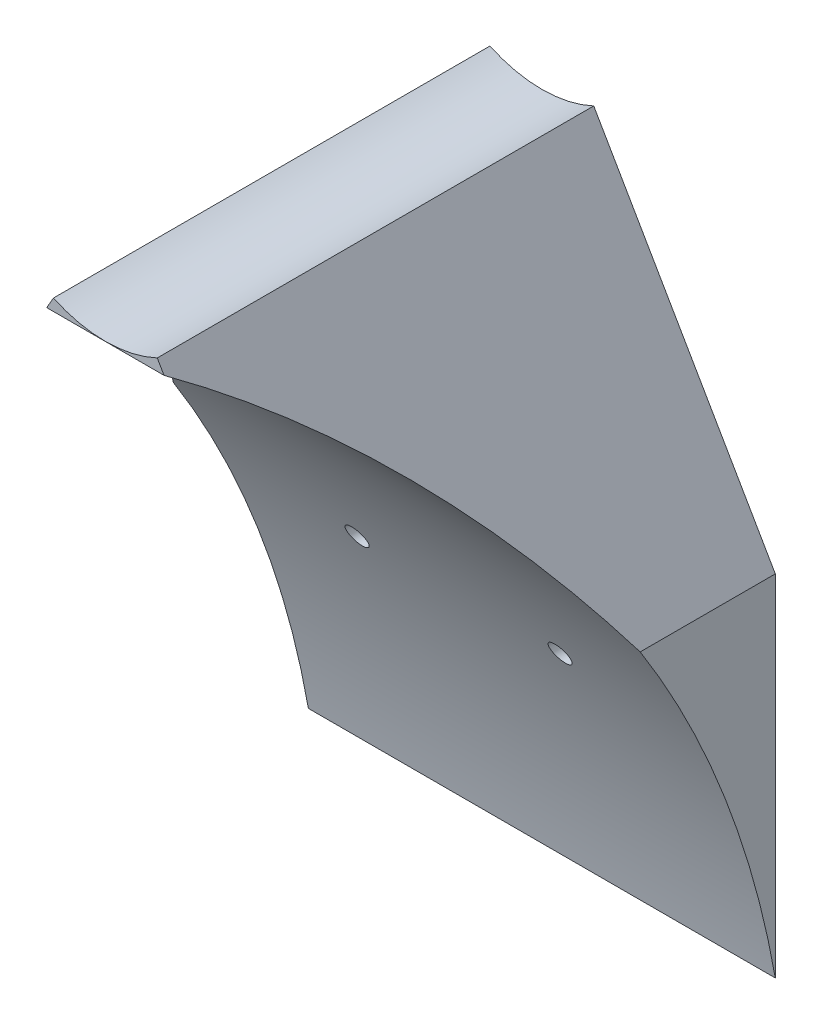
SolidWorks part; units mm, degrees
ref_plane "Front Plane" through (0, 0, 0) normal (0, 0, 1) x (1, 0, 0)
ref_plane "Top Plane" through (0, 0, 0) normal (0, 1, 0) x (1, 0, 0)
ref_plane "Right Plane" through (0, 0, 0) normal (1, 0, 0) x (0, 0, -1)
sketch "Sketch1" plane through (0, 0, 0) normal (0, 0, 1) x (1, 0, 0)
  line L0 (0, 0) -> (0, -127) construction
  line L1 (0, 0) -> (38.1, -65.9911) construction
  line L2 (0, 0) -> (-38.1, -65.9911) construction
  line L3 (-38.1, -65.9911) -> (-38.1, -121.1503) construction
  line L5 (0, 0) -> (0, -127) construction
  line L6 (38.1, -121.1503) -> (38.1, -65.9911) construction
  line L7 (38.1, -121.1503) -> (38.1, -159.2503) construction
  line L8 (-50.8, -197.3503) -> (0, -197.3503) construction
  line L9 (-50.8, -195.7628) -> (0, -195.7628) construction
  line L10 (36.5125, -121.1503) -> (36.5125, -159.2503) construction
  line L11 (36.5125, -121.1503) -> (36.5125, -66.4165)
  line L12 (0, -3.175) -> (36.5125, -66.4165)
  line L13 (0, -3.175) -> (-36.5125, -66.4165)
  line L14 (-36.5125, -66.4165) -> (-36.5125, -121.1503)
  line L15 (-36.5125, -121.1503) -> (-38.1, -121.1503) construction
  line L16 (-50.8, -195.7628) -> (-50.8, -197.3503) construction
  line L17 (36.5125, -121.1503) -> (-36.5125, -121.1503)
  circle A0 centre (0, 0) radius 127 construction
  circle A1 centre (0, 0) radius 76.2 construction
  arc A2 (38.1, -159.2503) -> (0, -197.3503) centre (0, -159.2503) cw construction
  arc A3 (36.5125, -159.2503) -> (0, -195.7628) centre (0, -159.2503) cw construction
  point P2 (-15.875, -74.528)
  point P12 (0, 0)
  point P14 (15.875, -74.528)
  point P25 (0, -38.1)
  dimension "D2" = 152.4
  dimension "D6" = 1.5875
  dimension "D1" = 127
  dimension "D3" = 38.1
  dimension "D4" = 50.8
  dimension "D5" = 60
  dimension "D7" = 38.1
  dimension "D8" = 31.75
extrude "Boss-Extrude1" add sketch "Sketch1" along normal blind 76.2
sketch "Sketch2" plane through (0, 0, 0) normal (1, 0, 0) x (0, 0, -1)
  line L3 (-76.2, -121.1503) -> (0, -121.1503) construction
  line L4 (-76.2, -121.1503) -> (-76.2, -66.4165) construction
  line L6 (-76.2, -121.1503) -> (0, -121.1503)
  line L7 (-76.2, -121.1503) -> (-76.2, -66.4165)
  line L10 (-76.2, -66.4165) -> (-76.2, -3.175) construction
  line L11 (-76.2, -22.225) -> (-76.2, -66.4165)
  line L12 (0, -66.4165) -> (0, -3.175) construction
  line L13 (-76.2, -3.175) -> (0, -3.175) construction
  line L14 (-68.2625, -19.0675) -> (-68.2625, -3.175)
  line L15 (-68.2625, -3.175) -> (-76.2, -3.175)
  line L16 (-76.2, -3.175) -> (-76.2, -22.225)
  arc A0 (-68.2625, -19.0675) -> (0, -121.1503) centre (-150.0796, -147.6432) cw
  dimension "D1" = 68.2625
  dimension "D2" = 152.4
extrude "Cut-Extrude1" cut sketch "Sketch2" along normal up to surface (36.5125 mm away) from surface up to face at (36.5125, -93.7834, 38.1) starting at face at (-36.5125, -93.7834, 38.1)
sketch "Sketch5" plane through (0, 0, 0) normal (0, 0, 1) x (1, 0, 0)
  line L0 (0, -82.55) -> (0, 0) construction
  circle A0 centre (0, 0) radius 82.55 construction
  point P0 (0, -38.1)
  point P4 (-15.875, -81.0092)
  point P5 (15.875, -81.0092)
  dimension "D1" = 38.1
  dimension "D3" = 165.1
  dimension "D2" = 31.75
hole_wizard "M3 Clearance Hole1" positions "Sketch7" profile "Sketch8" hole size "M3" standard "ANSI Metric" end condition through all
sketch "Sketch7" plane through (0, 0, 0) normal (0, 0, -1) x (-1, 0, 0)
  point P0 (-15.875, -81.0092)
  point P3 (15.875, -81.0092)
  point P6 (0, -38.1)
sketch "Sketch8" plane through (15.875, -81.0092, 0) normal (1, 0, 0) x (0, 1, 0)
  line L0 (0, 0) -> (0, 68.2625)
  line L1 (0, 68.2625) -> (1.7, 68.2625)
  line L2 (1.7, 68.2625) -> (1.7, 0)
  line L5 (1.7, 0) -> (0, 0)
  line L11 (0, -6.35) -> (0, 107.95) construction
  dimension "Thru Hole Dia." = 3.4
  dimension "Thru Hole Depth" = 68.2625
sketch "Sketch10" plane through (0, 0, 0) normal (0, 0, -1) x (-1, 0, 0)
  circle A0 centre (0, 0) radius 19.05
  dimension "D1" = 38.1
extrude "Cut-Extrude2" cut sketch "Sketch10" against normal up to next
